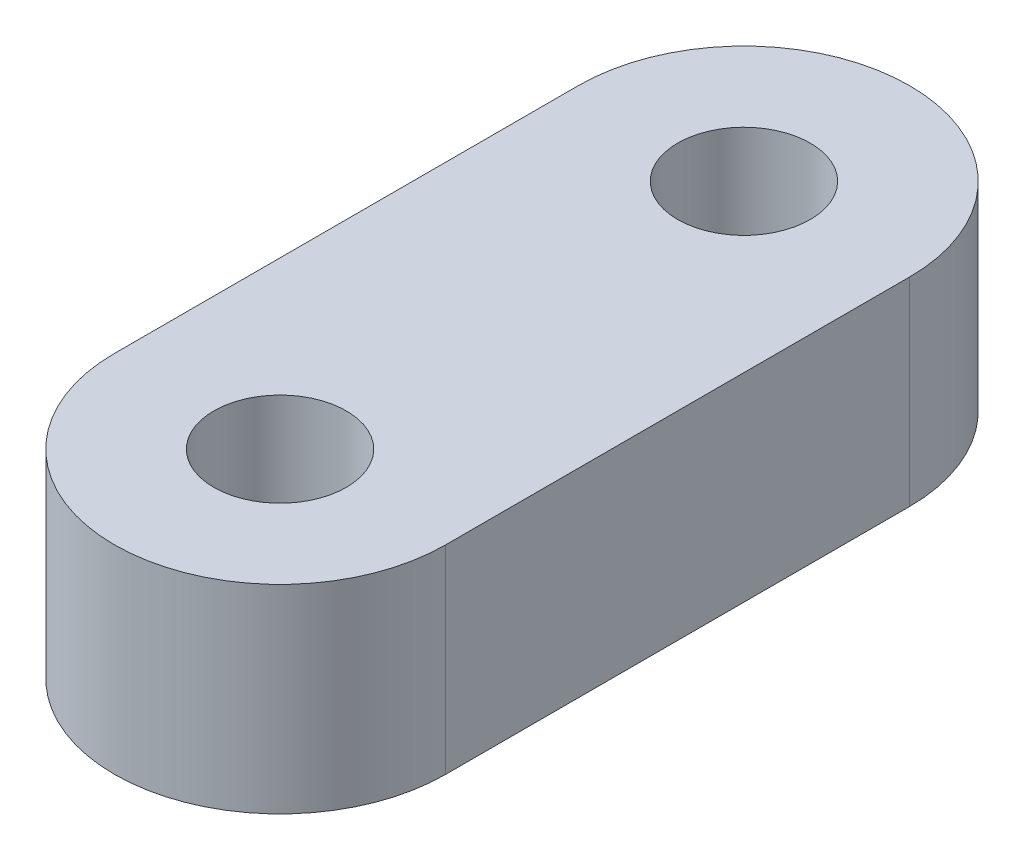
SolidWorks part; units mm, degrees
ref_plane "Alzado" through (0, 0, 0) normal (0, 0, 1) x (1, 0, 0)
ref_plane "Planta" through (0, 0, 0) normal (0, 1, 0) x (1, 0, 0)
ref_plane "Vista lateral" through (0, 0, 0) normal (1, 0, 0) x (0, 0, -1)
sketch "Croquis1" plane through (0, 0, 0) normal (0, 1, 0) x (1, 0, 0)
  line L0 (0, -3.5) -> (0, 3.5) construction
  line L1 (-2.5, -3.5) -> (-2.5, 3.5)
  line L2 (2.5, -3.5) -> (2.5, 3.5)
  arc A0 (-2.5, -3.5) -> (2.5, -3.5) centre (0, -3.5) ccw
  arc A1 (2.5, 3.5) -> (-2.5, 3.5) centre (0, 3.5) ccw
  circle A2 centre (0, 3.5) radius 1
  circle A3 centre (0, -3.5) radius 1
  point P2 (0, 0)
  dimension "D3" = 2
  dimension "D1" = 7
  dimension "D2" = 5
sheet metal parameters "Chapa metálica1" thickness 3 parameters "D1"=0.7366, "Espesor"=3
base flange "Brida base1" sketch "Croquis1" thickness 3 reverse thickness direction no parameters "D1"=0.7366
flat pattern "Chapa desplegada1" [suppressed]
sketch "Líneas de pliegue1" plane through (0, 0, 0) normal (0, 1, 0) x (-1, 0, 0)
sketch3d "Cuadro delimitador1" [suppressed]
  line L0 (-2.5, -12.4995, 0) -> (-2.5, 2.4995, 0) construction
  line L1 (2.5, -12.4995, 0) -> (2.5, 2.4995, 0) construction
  line L2 (-2.5, -12.4995, 0) -> (2.5, -12.4995, 0) construction
  line L3 (-2.5, 2.4995, 0) -> (2.5, 2.4995, 0) construction
